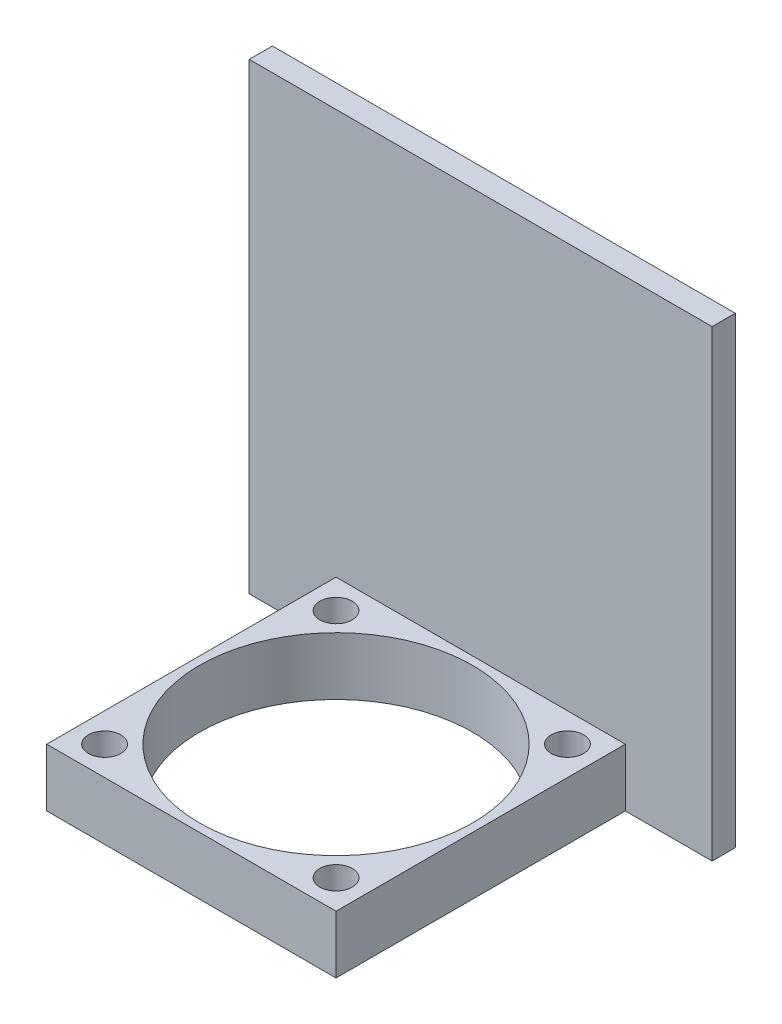
SolidWorks part; units mm, degrees
ref_plane "Front Plane" through (0, 0, 0) normal (1, 0, 0) x (0, 1, 0)
ref_plane "Top Plane" through (0, 0, 0) normal (0, 0, 1) x (0, 1, 0)
ref_plane "Right Plane" through (0, 0, 0) normal (0, 1, 0) x (-1, 0, 0)
sketch "Sketch2" plane through (0, 0, 0) normal (0, 0, 1) x (0, 1, 0)
  line L1 (-20, -20) -> (20, -20)
  line L2 (-20, -20) -> (-20, 20)
  line L3 (-20, 20) -> (20, 20)
  line L4 (20, -20) -> (20, 20)
  line L5 (-20, -20) -> (20, 20) construction
  line L6 (-20, 20) -> (20, -20) construction
  line L11 (-25, 12.5) -> (-15, -12.5) construction
  line L12 (-25, -12.5) -> (-15, 12.5) construction
  line L13 (-15, 12.5) -> (-5, 12.5)
  line L14 (-15, 12.5) -> (-15, -12.5)
  line L15 (-15, -12.5) -> (-5, -12.5)
  line L16 (-5, 12.5) -> (-5, -12.5)
  line L17 (20, 12.5) -> (5.2, 12.5)
  line L18 (20, 12.5) -> (20, -12.5)
  line L19 (20, -12.5) -> (5.2, -12.5)
  line L20 (5.2, 12.5) -> (5.2, -12.5)
  line L21 (-20, 12.5) -> (-15, 12.5)
  line L22 (-20, 12.5) -> (-20, -12.5)
  line L23 (-20, -12.5) -> (-15, -12.5)
  line L24 (-15, 12.5) -> (-15, -12.5)
  point P0 (0, 0)
  point P6 (-20, 0)
  dimension "D1" = 40
  dimension "D2" = 40
  dimension "D3" = 25
  dimension "D4" = 10
  dimension "D5" = 10
  dimension "D6" = 14.8
extrude "Boss-Extrude1" add sketch "Sketch2" along normal blind 25 contours L2 L23 L14 L21 region at (0, -17.5, 0)
extrude "Boss-Extrude2" add sketch "Sketch2<3>" against normal blind 2 contours L3 L4 L1 L2
sketch "Sketch2<3>" plane through (0, 0, 0) normal (0, 0, 1) x (0, 1, 0) same geometry as "Sketch2"
sketch "Sketch3" plane through (0, -20, 0) normal (0, -1, 0) x (1, 0, 0)
  line L1 (-12.5, 25) -> (12.5, 25)
  line L2 (-12.5, 25) -> (-12.5, 0)
  line L3 (-12.5, 0) -> (12.5, 0)
  line L4 (12.5, 25) -> (12.5, 0)
  circle A0 centre (0, 12.5) radius 11.8
  circle A1 centre (-10, 22.5) radius 1.4
  circle A2 centre (10, 22.5) radius 1.4
  circle A3 centre (10, 2.5) radius 1.4
  circle A4 centre (-10, 2.5) radius 1.4
  dimension "D1" = 4
extrude "Cut-Extrude1" cut sketch "Sketch3" against normal blind 21 and the other way through all contours A1 | A0 | A2 | A3 | A4 region at (0, -20, 12.5) region at (-10, -20, 22.5) region at (10, -20, 22.5) region at (10, -20, 2.5) region at (-10, -20, 2.5)
sketch "Sketch6" plane through (20, 0, 0) normal (1, 0, 0) x (0, 1, 0)
  line L1 (20, 0) -> (18, 0)
  line L2 (20, 0) -> (20, 25)
  line L3 (20, 25) -> (18, 25)
  line L4 (18, 0) -> (18, 25)
  dimension "D1" = 25
  dimension "D2" = 2
